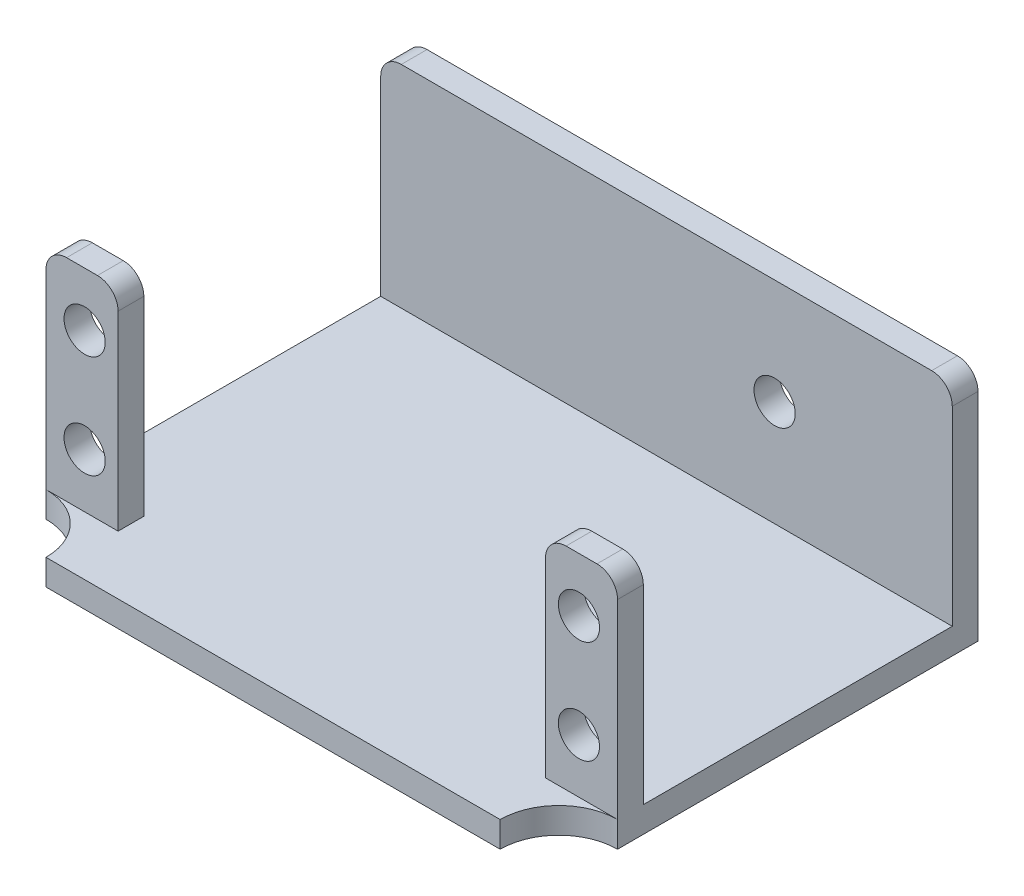
SolidWorks part; units mm, degrees
ref_plane "Front" through (0, 0, 0) normal (0, 0, 1) x (1, 0, 0)
ref_plane "Top" through (0, 0, 0) normal (0, 1, 0) x (1, 0, 0)
ref_plane "Right" through (0, 0, 0) normal (1, 0, 0) x (0, 0, -1)
sketch "Sketch1" plane through (0, 0, 0) normal (0, 1, 0) x (1, 0, 0)
  line L1 (0, 0) -> (55.5, 0)
  line L2 (0, 0) -> (0, 38.2)
  line L3 (0, 38.2) -> (55.5, 38.2)
  line L4 (55.5, 0) -> (55.5, 38.2)
  dimension "D1" = 38.2
  dimension "D2" = 55.5
extrude "bracketBase" add sketch "Sketch1" along normal blind 2.5
ref_plane "referencePlane1" through (0, 0, -8.2) normal (0, 0, 1) x (1, 0, 0)
sketch "Sketch2" plane through (0, 0, -8.2) normal (0, 0, 1) x (1, 0, 0)
  line L0 (27.75, 2.5) -> (27.75, 23) construction
  line L1 (0, 2.5) -> (7, 2.5)
  line L2 (0, 2.5) -> (0, 23)
  line L3 (0, 23) -> (7, 23)
  line L4 (7, 2.5) -> (7, 23)
  line L5 (0, 2.5) -> (55.5, 2.5) construction
  line L6 (55.5, 23) -> (48.5, 23)
  line L7 (48.5, 2.5) -> (48.5, 23)
  line L8 (55.5, 2.5) -> (48.5, 2.5)
  line L9 (55.5, 2.5) -> (55.5, 23)
  dimension "D1" = 20.5
  dimension "D2" = 7
extrude "servoMountingHoleTabs" add sketch "Sketch2" along normal blind 2.5
sketch "Sketch3" plane through (0, 0, -5.7) normal (0, 0, 1) x (1, 0, 0)
  line L0 (0, 12.75) -> (7, 12.75) construction
  line L3 (0, 23) -> (0, 2.5) construction
  line L4 (7, 2.5) -> (7, 23) construction
  line L5 (7, 23) -> (0, 23) construction
  line L6 (27.75, 2.5) -> (27.75, 23) construction
  line L7 (0, 2.5) -> (55.5, 2.5) construction
  circle A0 centre (3.75, 17.75) radius 2
  circle A1 centre (3.75, 7.75) radius 2
  circle A2 centre (51.75, 7.75) radius 2
  circle A3 centre (51.75, 17.75) radius 2
  dimension "D1" = 4
  dimension "D2" = 3.75
  dimension "D3" = 5.25
extrude "servoMountingHoles" cut sketch "Sketch3" against normal blind 2.5
sketch "Sketch4" plane through (0, 0, 0) normal (0, 1, 0) x (1, 0, 0)
  line L0 (55.5, 8.2) -> (55.5, 38.2) construction
  line L1 (0, 38.2) -> (55.5, 38.2)
  line L2 (0, 38.2) -> (0, 40.7)
  line L3 (0, 40.7) -> (55.5, 40.7)
  line L4 (55.5, 38.2) -> (55.5, 40.7)
  dimension "D1" = 2.5
extrude "baseWall" add sketch "Sketch4" along normal up to surface (23 mm away) up to face at (3.5, 23, -6.95)
sketch "Sketch6" plane through (0, 2.5, 0) normal (0, 1, 0) x (1, 0, 0)
  circle A0 centre (0, 0) radius 5.7
  circle A1 centre (55.5, 0) radius 5.7
extrude "baseTrim" cut sketch "Sketch6" against normal blind 2.5
fillet "Fillet1" radius 2 6 edges at (7, 23, -6.95) (48.5, 23, -6.95) (0, 23, -6.95) (55.5, 23, -6.95) (55.5, 23, -39.45) (0, 23, -39.45)
sketch "Sketch7" plane through (0, 0, -40.7) normal (0, 0, -1) x (-1, 0, 0)
  line L0 (0, 21) -> (0, 0) construction
  line L1 (-55.5, 0) -> (0, 0) construction
  circle A0 centre (-17.25, 12.75) radius 2
  dimension "D1" = 4
  dimension "D2" = 17.25
  dimension "D3" = 12.75
extrude "M4mountingHole" cut sketch "Sketch7" against normal blind 10
sketch "Sketch8" plane through (0, 0, -40.7) normal (0, 0, -1) x (-1, 0, 0)
  line L0 (-27.75, 23) -> (-27.75, 0) construction
  line L1 (-2, 23) -> (-53.5, 23) construction
  line L2 (-55.5, 0) -> (0, 0) construction
  circle A0 centre (-17.25, 12.75) radius 2 construction
  circle A1 centre (-17.25, 12.75) radius 2 construction
  circle A2 centre (-38.25, 12.75) radius 2
extrude "Cut-Extrude1" cut sketch "Sketch8" against normal blind 10
sketch "Sketch9" plane through (0, 0, -40.7) normal (0, 0, -1) x (-1, 0, 0)
  circle A0 centre (-17.25, 12.75) radius 2 construction
  circle A1 centre (-17.25, 12.75) radius 2
extrude "Boss-Extrude1" add sketch "Sketch9" against normal up to surface (2.5 mm away) up to face at (36.25, 12.75, -38.2)
